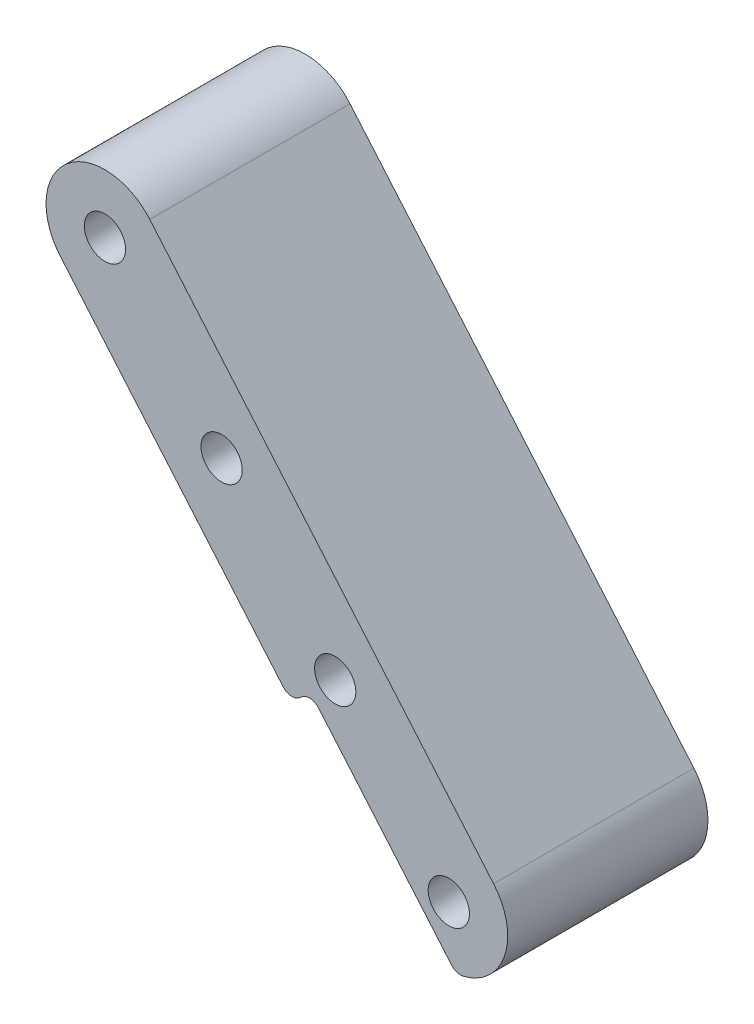
SolidWorks part; units mm, degrees
ref_plane "前视基准面" through (0, 0, 0) normal (0, 0, 1) x (1, 0, 0)
ref_plane "上视基准面" through (0, 0, 0) normal (0, 1, 0) x (1, 0, 0)
ref_plane "右视基准面" through (0, 0, 0) normal (1, 0, 0) x (0, 0, -1)
other "Configuration Table"
sketch "草图1" plane through (0, 0, 0) normal (0, 0, 1) x (1, 0, 0)
  line L15 (44.7669, -56.8983) -> (91.6346, -112.753)
  line L20 (91.2489, -112.0412) -> (90.3686, -110.2637)
  line L22 (33.7211, -44.8147) -> (92.0987, -113.3062) construction
  line L23 (41.3317, -38.3279) -> (99.7094, -106.8194)
  line L24 (26.1105, -51.3015) -> (84.4881, -119.793)
  circle A47 centre (33.7211, -44.8147) radius 3.5
  circle A48 centre (53.5315, -67.3435) radius 3.5
  circle A50 centre (72.8151, -90.3249) radius 3.5
  circle A52 centre (92.0987, -113.3062) radius 3.5
  arc A61 (91.2489, -112.0412) -> (91.6346, -112.753) centre (289.2645, -5.2012) ccw
  arc A66 (44.7669, -56.8983) -> (28.5093, -39.4853) centre (-127.5931, -201.5255) ccw
  arc A67 (41.3317, -38.3279) -> (26.1105, -51.3015) centre (33.7211, -44.8147) ccw
  arc A68 (84.4881, -119.793) -> (99.7094, -106.8194) centre (92.0987, -113.3062) ccw
  point P0 (62.9099, -79.0605)
  dimension "D1" = 10
  dimension "D2" = 7
  dimension "D3" = 7
  dimension "D4" = 7
  dimension "D8" = 7
  dimension "D5" = 30
  dimension "D6" = 30
  dimension "D7" = 30
extrude "凸台-拉伸3" add sketch "草图1" along normal blind 34 contours A47 L22 A48 L15 A66 | L24 A68 L23 A67 L22 A47 A66 L15 A48 A50 A52 | A48 L22 A50 L15 | A50 L22 A52 L15 region at (43.939, -56.4033, 0) region at (62.4051, -78.1948, 0) region at (80.514, -99.6077, 0) region at (62.9922, -79.182, 0)
sketch "草图2" plane through (0, 0, 34) normal (0, 0, 1) x (1, 0, 0)
  line L0 (93.3304, -123.2301) -> (68.6806, -94.3097)
  line L1 (68.6806, -94.3097) -> (65.2558, -97.2288)
  line L2 (26.1105, -51.3015) -> (84.4881, -119.793)
  line L3 (99.7094, -106.8194) -> (41.3317, -38.3279)
  line L4 (26.1105, -51.3015) -> (84.4881, -119.793)
  line L5 (99.7094, -106.8194) -> (41.3317, -38.3279)
  arc A2 (84.4881, -119.793) -> (99.7094, -106.8194) centre (92.0987, -113.3062) ccw
  arc A3 (41.3317, -38.3279) -> (26.1105, -51.3015) centre (33.7211, -44.8147) ccw
  arc A4 (84.4881, -119.793) -> (99.7094, -106.8194) centre (92.0987, -113.3062) ccw
  arc A5 (41.3317, -38.3279) -> (26.1105, -51.3015) centre (33.7211, -44.8147) ccw
  line M9 (26.1105, -51.3015) -> (84.4881, -119.793)
  arc M10 (84.4881, -119.793) -> (99.7094, -106.8194) centre (92.0987, -113.3062) ccw
  dimension "D2" = 38
  dimension "D3" = 4.5
  dimension "D1" = 0
extrude "切除-拉伸1" cut sketch "草图2" against normal through all contours L0 L1 M9 M10 region at (78.5764, -109.2839, 34)
fillet "圆角1" radius 2 3 edges at (65.2558, -97.2288, 17) (93.3304, -123.2301, 17) (68.6806, -94.3097, 17)
